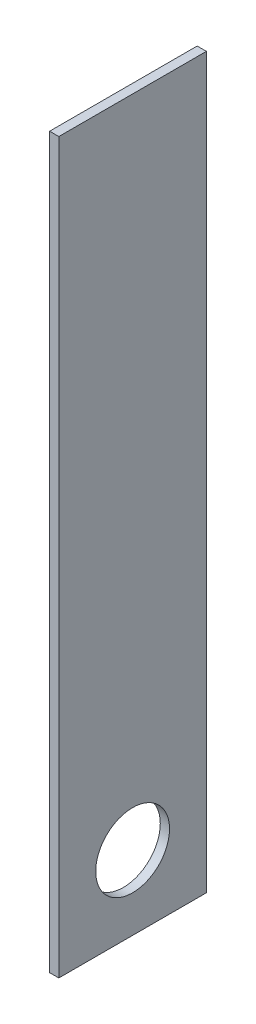
SolidWorks part; units mm, degrees
material "6063-O"
ref_plane "Front" through (0, 0, 0) normal (0, 0, 1) x (1, 0, 0)
ref_plane "Top" through (0, 0, 0) normal (0, 1, 0) x (1, 0, 0)
ref_plane "Right" through (0, 0, 0) normal (1, 0, 0) x (0, 0, -1)
sketch "Sketch1" plane through (0, 0, 0) normal (1, 0, 0) x (0, 0, -1)
  line L0 (0, 125.4125) -> (0, -125.4125) construction
  line L1 (-25.4, 125.4125) -> (25.4, 125.4125)
  line L2 (-25.4, 125.4125) -> (-25.4, -125.4125)
  line L3 (-25.4, -125.4125) -> (25.4, -125.4125)
  line L4 (25.4, 125.4125) -> (25.4, -125.4125)
  circle A0 centre (0, -100.0125) radius 12.7
  point P4 (0, 0)
  dimension "D3" = 25.4
  dimension "D1" = 50.8
  dimension "D2" = 250.825
  dimension "D4" = 25.4
extrude "Boss-Extrude1" add sketch "Sketch1" along normal blind 3.175
